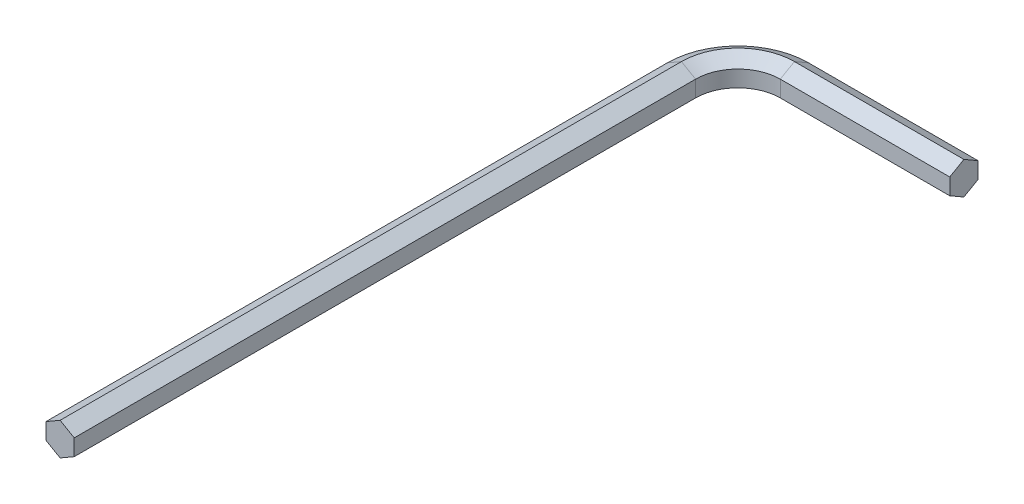
SolidWorks part; units mm, degrees
ref_plane "Front Plane" through (0, 0, 0) normal (0, 0, 1) x (1, 0, 0)
ref_plane "Top Plane" through (0, 0, 0) normal (0, 1, 0) x (1, 0, 0)
ref_plane "Right Plane" through (0, 0, 0) normal (1, 0, 0) x (0, 0, -1)
sketch "Sketch1" plane through (0, 0, 0) normal (0, 1, 0) x (1, 0, 0)
  line L0 (0, 0) -> (0, 60) construction
  line L1 (0, 60) -> (20, 60) construction
  line L2 (0, 0) -> (0, 55)
  line L3 (5, 60) -> (20, 60)
  arc A0 (0, 55) -> (5, 60) centre (5, 55) cw
  dimension "D3" = 5
  dimension "D1" = 60
  dimension "D2" = 20
sketch "Sketch2" plane through (0, 0, 0) normal (0, 0, 1) x (1, 0, 0)
  line L0 (0, 0) -> (0, 1.4434) construction
  line L1 (0, 0) -> (0, -1.4434) construction
  line L2 (0, 1.4434) -> (-1.25, 0.7217)
  line L3 (-1.25, 0.7217) -> (-1.25, -0.7217)
  line L4 (-1.25, -0.7217) -> (0, -1.4434)
  line L5 (0, -1.4434) -> (1.25, -0.7217)
  line L6 (1.25, -0.7217) -> (1.25, 0.7217)
  line L7 (1.25, 0.7217) -> (0, 1.4434)
  line L8 (0, 0) -> (1.25, 0.7217) construction
  line L9 (0, 0) -> (1.25, -0.7217) construction
  line L10 (0, 0) -> (-1.25, 0.7217) construction
  line L11 (-1.25, -0.7217) -> (0, 0) construction
  line L12 (-1.25, 0) -> (0, 0) construction
  dimension "D1" = 2.5
sweep "Sweep1" add profiles "Sketch2" path "Sketch1"
ref_axis "Axis1" through (0, 0, 3.0625) along (0, 0, -1)
